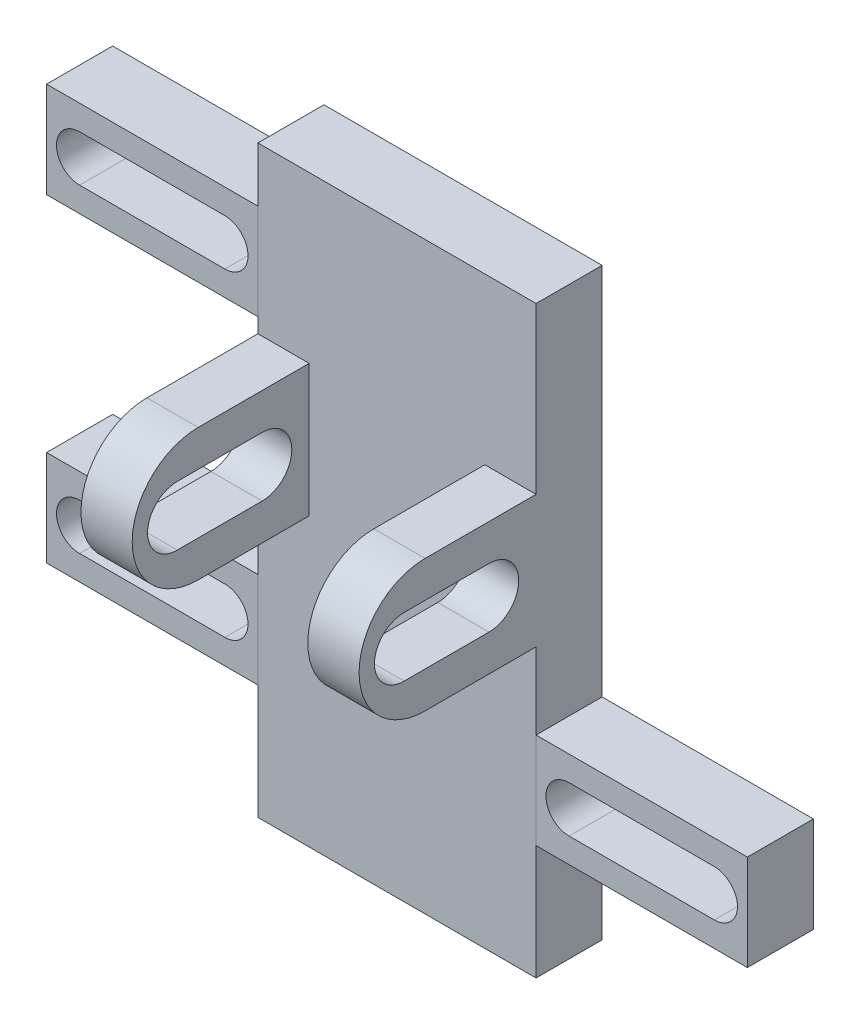
SolidWorks part; units mm, degrees
ref_plane "Front Plane" through (0, 0, 0) normal (0, 0, 1) x (1, 0, 0)
ref_plane "Top Plane" through (0, 0, 0) normal (0, 1, 0) x (1, 0, 0)
ref_plane "Right Plane" through (0, 0, 0) normal (1, 0, 0) x (0, 0, -1)
sketch "Sketch1" plane through (0, 0, 0) normal (0, 0, 1) x (1, 0, 0)
  line L0 (4692.3212, -62.8445) -> (4650.9212, -62.8445) construction
  line L1 (4661.0828, -18.6148) -> (4682.1433, -18.6148)
  line L2 (4661.0828, -18.6148) -> (4661.0828, -62.8445)
  line L3 (4661.0828, -62.8445) -> (4682.1433, -62.8445)
  line L4 (4682.1433, -18.6148) -> (4682.1433, -62.8445)
  line L5 (4661.0828, -27.1456) -> (4658.9212, -27.1456) construction
  line L6 (4658.9212, -12.4285) -> (4658.9212, -50.5381) construction
  line L7 (4682.1433, -34.3161) -> (4684.3037, -34.2412) construction
  line L8 (4684.3037, -50.5381) -> (4684.3037, -12.4285) construction
extrude "Boss-Extrude1" add sketch "Sketch1" along normal blind 5
sketch "Sketch2" plane through (0, 0, 0) normal (0, 0, -1) x (-1, 0, 0)
  line L0 (-4671.6212, -59.6913) -> (-4671.6212, -53.6913) construction
  line L1 (-4664.1212, -59.6913) -> (-4679.1212, -59.6913) construction
  line L2 (-4679.1212, -53.6913) -> (-4664.1212, -53.6913) construction
  line L4 (-4674.1212, -53.8163) -> (-4669.1212, -53.8163)
  line L5 (-4674.1212, -53.8163) -> (-4674.1212, -59.5663)
  line L6 (-4674.1212, -59.5663) -> (-4669.1212, -59.5663)
  line L7 (-4669.1212, -53.8163) -> (-4669.1212, -59.5663)
  line L8 (-4674.1212, -53.8163) -> (-4669.1212, -59.5663) construction
  line L9 (-4674.1212, -59.5663) -> (-4669.1212, -53.8163) construction
  point P6 (-4671.6212, -56.6913)
  dimension "D1" = 5.75
  dimension "D2" = 5
extrude "Boss-Extrude2" add sketch "Sketch2" along normal blind 8
sketch "Sketch4" plane through (4661.0828, 0, 0) normal (-1, 0, 0) x (0, 0, 1)
  line L3 (5, -18.6148) -> (5, -62.8445) construction
  line L4 (13.4005, -31.1292) -> (5, -31.1292)
  line L6 (13.4005, -41.1292) -> (5, -41.1292)
  line L7 (5, -31.1292) -> (5, -41.1292)
  arc A0 (13.4005, -41.1292) -> (13.4005, -31.1292) centre (13.4005, -36.1292) ccw
  dimension "D1" = 5
extrude "Boss-Extrude3" add sketch "Sketch4" against normal blind 3.8801
sketch "Sketch5" plane through (4664.9629, 0, 0) normal (1, 0, 0) x (0, 0, -1)
  line L0 (-14.9864, -36.1292) -> (-8.5634, -36.1292) construction
  line L1 (-14.9864, -33.8792) -> (-8.5634, -33.8792)
  line L2 (-14.9864, -38.3792) -> (-8.5634, -38.3792)
  line L3 (-13.4005, -36.1292) -> (-8.9343, -36.1292) construction
  arc A1 (-14.9864, -33.8792) -> (-14.9864, -38.3792) centre (-14.9864, -36.1292) ccw
  arc A2 (-8.5634, -38.3792) -> (-8.5634, -33.8792) centre (-8.5634, -36.1292) ccw
  point P3 (-11.7749, -36.1292)
  dimension "D1" = 2.25
  dimension "D2" = 1.6257
  dimension "D3" = 4.8372
extrude "Cut-Extrude1" cut sketch "Sketch5" against normal blind 8
ref_plane "Plane1" through (4671.6131, 0, 0) normal (-1, 0, 0) x (0, 0, 1)
mirror "Mirror2" about plane through (4671.6131, 0, 0) normal (-1, 0, 0) of "Cut-Extrude1", "Boss-Extrude3"
sketch "Sketch6" plane through (0, 0, 5) normal (0, 0, 1) x (1, 0, 0)
  line L0 (4688.3131, -48.9131) -> (4688.3131, -52.1631) construction
  line L1 (4682.1433, -46.9131) -> (4698.1433, -46.9131)
  line L2 (4682.1433, -46.9131) -> (4682.1433, -54.1631)
  line L3 (4682.1433, -54.1631) -> (4698.1433, -54.1631)
  line L4 (4698.1433, -46.9131) -> (4698.1433, -54.1631)
  line L5 (4658.9131, -50.5381) -> (4684.2955, -50.5381) construction
  line L6 (4688.3131, -52.1631) -> (4688.3131, -54.1631) construction
  line L7 (4688.3131, -48.9131) -> (4688.3131, -46.9131) construction
  line L8 (4658.4131, -50.5381) -> (4684.8131, -50.5381) construction
  line L9 (4695.6433, -50.5381) -> (4684.6433, -50.5381) construction
  line L10 (4695.6433, -52.2881) -> (4684.6433, -52.2881)
  line L11 (4695.6433, -48.7881) -> (4684.6433, -48.7881)
  line L12 (4686.6881, -50.5381) -> (4689.9381, -50.5381) construction
  line L13 (4695.6433, -52.2881) -> (4698.1433, -52.2881) construction
  line L14 (4682.1433, -62.8445) -> (4682.1433, -41.1292) construction
  line L15 (4661.0828, -18.6148) -> (4661.0828, -31.1292) construction
  line L16 (4682.1433, -18.6148) -> (4661.0828, -18.6148) construction
  arc A1 (4695.6433, -52.2881) -> (4695.6433, -48.7881) centre (4695.6433, -50.5381) ccw
  arc A2 (4684.6433, -48.7881) -> (4684.6433, -52.2881) centre (4684.6433, -50.5381) ccw
  circle A3 centre (4688.3131, -50.5381) radius 1.625 construction
  point P18 (4690.1433, -50.5381)
  dimension "D2" = 16
  dimension "D3" = 11
  dimension "D1" = 1.75
  dimension "D4" = 2.5
  dimension "D5" = 27.2303
  dimension "D6" = 28.2983
  dimension "D7" = 35.5483
extrude "Boss-Extrude4" add sketch "Sketch6" against normal blind 5 separate body
ref_plane "Plane2" through (4671.6131, 0, 0) normal (-1, 0, 0) x (0, 0, 1)
mirror "Mirror3" about plane through (4671.6131, 0, 0) normal (-1, 0, 0) of bodies 107
ref_plane "Plane3" through (0, -24.872, 0) normal (0, -1, 0) x (-1, 0, 0)
sketch "Sketch9" plane through (0, 0, 5) normal (0, 0, 1) x (1, 0, 0)
  line L0 (4671.6131, -62.8445) -> (4671.6131, -18.6148) construction
  line L1 (4661.0828, -62.8445) -> (4682.1433, -62.8445) construction
  line L2 (4682.1433, -18.6148) -> (4661.0828, -18.6148) construction
  line L3 (4671.6131, -40.7297) -> (4677.5932, -40.7297) construction
  point P8 (0, 0)
ref_plane "Plane4" through (0, -40.7297, 0) normal (0, -1, 0) x (-1, 0, 0)
sketch "Sketch10" plane through (0, 0, 5) normal (0, 0, 1) x (1, 0, 0)
  line L0 (4654.9131, -26.3852) -> (4654.9131, -50.5381) construction
  line L1 (4654.9131, -38.4617) -> (4652.351, -38.4617) construction
ref_plane "Plane5" through (0, -38.4617, 0) normal (0, -1, 0) x (-1, 0, 0)
mirror "Mirror4" about plane through (0, -38.4617, 0) normal (0, -1, 0) of bodies 109 107
sketch "Sketch11" plane through (0, 0, 5) normal (0, 0, 1) x (1, 0, 0)
  line L1 (4682.1433, -22.7602) -> (4698.1433, -22.7602)
  line L2 (4682.1433, -22.7602) -> (4682.1433, -30.0102)
  line L3 (4682.1433, -30.0102) -> (4698.1433, -30.0102)
  line L4 (4698.1433, -22.7602) -> (4698.1433, -30.0102)
extrude "Cut-Extrude2" cut sketch "Sketch11" against normal up to vertex (5 mm away) up to point (4682.1433, -22.7602, 0)
